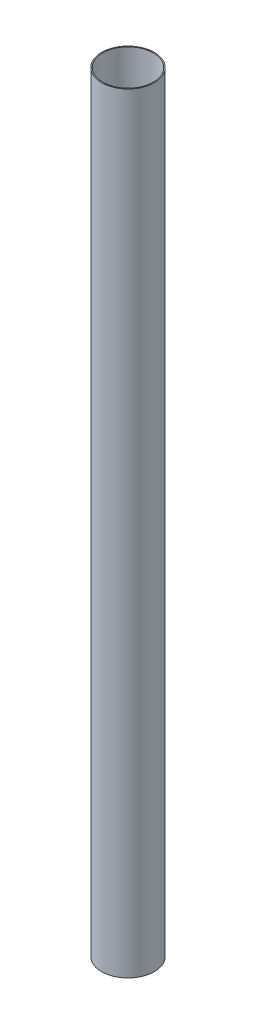
SolidWorks part; units mm, degrees
material "Plástico personalizado"
ref_plane "Plano frontal" through (0, 0, 0) normal (0, 0, 1) x (1, 0, 0)
ref_plane "Plano superior" through (0, 0, 0) normal (0, 1, 0) x (1, 0, 0)
ref_plane "Plano direito" through (0, 0, 0) normal (1, 0, 0) x (0, 0, -1)
sketch "Esboço1" plane through (0, 0, 0) normal (0, 1, 0) x (1, 0, 0)
  circle A0 centre (0, 0) radius 26
  circle A1 centre (0, 0) radius 25
extrude "Ressalto-extrusão1" add sketch "Esboço1" along normal blind 760 contours A0 | A1
